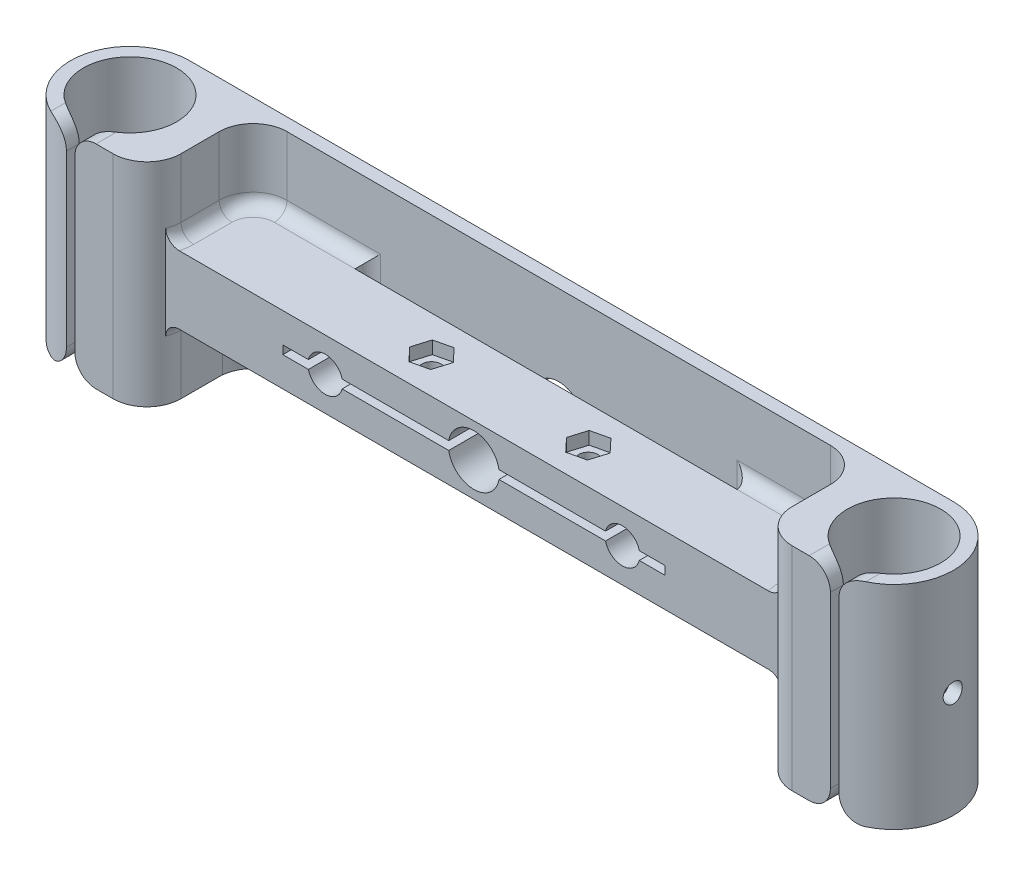
SolidWorks part; units mm, degrees
ref_plane "Front Plane" through (0, 0, 0) normal (0, 0, 1) x (1, 0, 0)
ref_plane "Top Plane" through (0, 0, 0) normal (0, 1, 0) x (1, 0, 0)
ref_plane "Right Plane" through (0, 0, 0) normal (1, 0, 0) x (0, 0, -1)
sketch "Sketch1" plane through (0, 0, 0) normal (0, 1, 0) x (1, 0, 0)
  line L0 (137.4606, -14.5) -> (119.4606, -14.5)
  line L1 (119.4606, -14.5) -> (119.4606, 10.5)
  line L2 (-42.5394, -14.5) -> (-24.5394, -14.5)
  line L3 (-42.5394, 13.5) -> (137.4606, 13.5)
  line L4 (119.4606, 10.5) -> (-24.5394, 10.5)
  line L5 (-24.5394, -14.5) -> (-24.5394, 10.5)
  circle A0 centre (-42.5394, -0.5) radius 11
  circle A1 centre (137.4606, -0.5) radius 11
  arc A2 (-42.5394, -14.5) -> (-42.5394, 13.5) centre (-42.5394, -0.5) cw
  arc A6 (137.4606, 13.5) -> (137.4606, -14.5) centre (137.4606, -0.5) cw
  dimension "D3" = 22
  dimension "D4" = 22
  dimension "D5" = 180
  dimension "D6" = 3
  dimension "D1" = 18
  dimension "D2" = 18
  dimension "D8" = 3
extrude "Boss-Extrude1" add sketch "Sketch1" along normal blind 100
fillet "Fillet1" radius 8 4 edges at (119.4606, 50, -10.5) (119.4606, 50, 14.5) (-24.5394, 50, -10.5) (-24.5394, 50, 14.5)
sketch "Sketch2" plane through (0, 0, -10.5) normal (0, 0, 1) x (1, 0, 0)
  line L0 (47.4606, 100) -> (47.4606, 0) construction
  line L1 (-16.5394, 100) -> (111.4606, 100) construction
  line L2 (-16.5394, 0) -> (111.4606, 0) construction
  circle A0 centre (12.4606, 50) radius 4.1
  circle A1 centre (82.4606, 50) radius 4.1
  circle A2 centre (47.4606, 50) radius 6
  point P10 (47.4606, 50)
  dimension "D1" = 8.2
  dimension "D2" = 8.2
  dimension "D5" = 12
  dimension "D3" = 35
  dimension "D4" = 35
extrude "Cut-Extrude1" cut sketch "Sketch2" against normal blind 10
sketch "Sketch3" plane through (0, 0, -10.5) normal (0, 0, 1) x (1, 0, 0)
  line L0 (12.4606, 58) -> (82.4606, 58)
  line L1 (12.4606, 42) -> (82.4606, 42)
  line L2 (12.4606, 58) -> (-16.5394, 58)
  line L3 (-16.5394, 100) -> (-16.5394, 0) construction
  line L4 (-16.5394, 58) -> (-28.8663, 58)
  line L5 (-28.8663, 58) -> (-28.8663, 42)
  line L6 (-28.8663, 42) -> (12.4606, 42)
  line L7 (82.4606, 58) -> (124.1494, 58)
  line L8 (124.1494, 58) -> (124.1494, 42)
  line L9 (124.1494, 42) -> (82.4606, 42)
  circle A2 centre (12.4606, 50) radius 4.1
  circle A3 centre (82.4606, 50) radius 4.1
  circle A4 centre (47.4606, 50) radius 6
  dimension "D2" = 12
extrude "Boss-Extrude2" add sketch "Sketch3" along normal blind 20
fillet "Fillet2" radius 3 14 edges at (-24.6867, 42, 8.0281) (-24.5394, 42, 2) (-22.1963, 42, -8.1569) (119.6079, 42, 8.0281) (119.4606, 42, 2) (117.1174, 42, -8.1569) (119.6079, 58, 8.0281) (119.4606, 58, 2) (-24.6867, 58, 8.0281) (-24.5394, 58, 2) (-22.1963, 58, -8.1569) (47.4606, 58, -10.5) (47.4606, 42, -10.5) (117.1174, 58, -8.1569)
sketch "Sketch4" plane through (0, 0, 9.5) normal (0, 0, 1) x (1, 0, 0)
  line L0 (47.4606, 50) -> (2.4606, 50)
  line L1 (47.4606, 50) -> (92.4606, 50)
  dimension "D1" = 45
extrude "Cut-Extrude-Thin1" cut sketch "Sketch4" against normal up to surface (20 mm away) and the other way through all thin up to face at (47.4606, 19.5, -10.5) thin type mid plane wall 2
sketch "Sketch5" plane through (0, 42, 0) normal (0, -1, 0) x (-1, 0, 0)
  line L0 (-2.4606, 7.5) -> (-47.4606, 7.5)
  line L1 (16.5394, 7.5) -> (-111.4606, 7.5) construction
  line L2 (-47.4606, 7.5) -> (-92.4606, 7.5)
  dimension "D1" = 45
  dimension "D2" = 45
extrude "Cut-Extrude-Thin2" cut sketch "Sketch5" against normal blind 20 and the other way through all thin thin type one direction wall 3
fillet "Fillet3" radius 3 2 edges at (92.4606, 50, -10.5) (2.4606, 50, -10.5)
sketch "Sketch6" plane through (0, 49, 0) normal (0, 1, 0) x (1, 0, 0)
  line L0 (16.4368, 7.5) -> (41.5445, -9.5) construction
  line L1 (41.5445, -9.5) -> (53.3767, -9.5) construction
  line L2 (53.3767, -9.5) -> (78.4844, 7.5) construction
  circle A0 centre (28.9906, -1) radius 2.25
  circle A1 centre (65.9305, -1) radius 2.25
  dimension "D1" = 4.5
  dimension "D2" = 4.5
extrude "Cut-Extrude2" cut sketch "Sketch6" against normal through all both and the other way through all
sketch "Sketch7" plane through (0, 58, 0) normal (0, 1, 0) x (1, 0, 0)
  line L1 (33.1506, -0.0263) -> (30.2274, 3.0895)
  line L2 (30.2274, 3.0895) -> (26.0674, 2.1158)
  line L3 (26.0674, 2.1158) -> (24.8307, -1.9737)
  line L4 (24.8307, -1.9737) -> (27.7539, -5.0895)
  line L5 (27.7539, -5.0895) -> (31.9138, -4.1158)
  line L6 (31.9138, -4.1158) -> (33.1506, -0.0263)
  line L7 (70.0905, -0.0263) -> (67.1673, 3.0895)
  line L8 (67.1673, 3.0895) -> (63.0073, 2.1158)
  line L9 (63.0073, 2.1158) -> (61.7706, -1.9737)
  line L10 (61.7706, -1.9737) -> (64.6938, -5.0895)
  line L11 (64.6938, -5.0895) -> (68.8537, -4.1158)
  line L12 (68.8537, -4.1158) -> (70.0905, -0.0263)
  circle A0 centre (28.9906, -1) radius 3.7 construction
  circle A1 centre (65.9305, -1) radius 3.7 construction
  dimension "D1" = 7.4
  dimension "D2" = 7.4
extrude "Cut-Extrude3" cut sketch "Sketch7" against normal blind 3
sketch "Sketch8" plane through (0, 100, 0) normal (0, 1, 0) x (1, 0, 0)
  line L6 (119.4606, 2.5) -> (119.4606, -6.5)
  line L7 (127.4606, -14.5) -> (137.4606, -14.5)
  line L8 (137.4606, 13.5) -> (-42.5394, 13.5)
  line L9 (-42.5394, -14.5) -> (-32.5394, -14.5)
  line L10 (-24.5394, -6.5) -> (-24.5394, 2.5)
  line L11 (-16.5394, 10.5) -> (111.4606, 10.5)
  line L12 (119.4606, 2.5) -> (119.4606, -6.5)
  line L13 (127.4606, -14.5) -> (137.4606, -14.5)
  line L14 (137.4606, 13.5) -> (-42.5394, 13.5)
  line L15 (-42.5394, -14.5) -> (-32.5394, -14.5)
  line L16 (-24.5394, -6.5) -> (-24.5394, 2.5)
  line L17 (-16.5394, 10.5) -> (111.4606, 10.5)
  arc A6 (119.4606, -6.5) -> (127.4606, -14.5) centre (127.4606, -6.5) ccw
  arc A7 (137.4606, -14.5) -> (137.4606, 13.5) centre (137.4606, -0.5) ccw
  arc A8 (-42.5394, 13.5) -> (-42.5394, -14.5) centre (-42.5394, -0.5) ccw
  arc A9 (-32.5394, -14.5) -> (-24.5394, -6.5) centre (-32.5394, -6.5) ccw
  arc A10 (-16.5394, 10.5) -> (-24.5394, 2.5) centre (-16.5394, 2.5) ccw
  arc A11 (119.4606, 2.5) -> (111.4606, 10.5) centre (111.4606, 2.5) ccw
  arc A12 (119.4606, -6.5) -> (127.4606, -14.5) centre (127.4606, -6.5) ccw
  arc A13 (137.4606, -14.5) -> (137.4606, 13.5) centre (137.4606, -0.5) ccw
  arc A14 (-42.5394, 13.5) -> (-42.5394, -14.5) centre (-42.5394, -0.5) ccw
  arc A15 (-32.5394, -14.5) -> (-24.5394, -6.5) centre (-32.5394, -6.5) ccw
  arc A16 (-16.5394, 10.5) -> (-24.5394, 2.5) centre (-16.5394, 2.5) ccw
  arc A17 (119.4606, 2.5) -> (111.4606, 10.5) centre (111.4606, 2.5) ccw
  dimension "D1" = 0
extrude "Cut-Extrude4" cut sketch "Sketch8" against normal blind 25
sketch "Sketch9" plane through (0, 0, 0) normal (0, 1, 0) x (1, 0, 0)
  line L6 (127.4606, -14.5) -> (137.4606, -14.5)
  line L7 (119.4606, 2.5) -> (119.4606, -6.5)
  line L8 (-16.5394, 10.5) -> (111.4606, 10.5)
  line L9 (-24.5394, -6.5) -> (-24.5394, 2.5)
  line L10 (-42.5394, -14.5) -> (-32.5394, -14.5)
  line L11 (137.4606, 13.5) -> (-42.5394, 13.5)
  line L12 (127.4606, -14.5) -> (137.4606, -14.5)
  line L13 (119.4606, 2.5) -> (119.4606, -6.5)
  line L14 (-16.5394, 10.5) -> (111.4606, 10.5)
  line L15 (-24.5394, -6.5) -> (-24.5394, 2.5)
  line L16 (-42.5394, -14.5) -> (-32.5394, -14.5)
  line L17 (137.4606, 13.5) -> (-42.5394, 13.5)
  arc A6 (119.4606, -6.5) -> (127.4606, -14.5) centre (127.4606, -6.5) ccw
  arc A7 (119.4606, 2.5) -> (111.4606, 10.5) centre (111.4606, 2.5) ccw
  arc A8 (-16.5394, 10.5) -> (-24.5394, 2.5) centre (-16.5394, 2.5) ccw
  arc A9 (-32.5394, -14.5) -> (-24.5394, -6.5) centre (-32.5394, -6.5) ccw
  arc A10 (-42.5394, 13.5) -> (-42.5394, -14.5) centre (-42.5394, -0.5) ccw
  arc A11 (137.4606, -14.5) -> (137.4606, 13.5) centre (137.4606, -0.5) ccw
  arc A12 (119.4606, -6.5) -> (127.4606, -14.5) centre (127.4606, -6.5) ccw
  arc A13 (119.4606, 2.5) -> (111.4606, 10.5) centre (111.4606, 2.5) ccw
  arc A14 (-16.5394, 10.5) -> (-24.5394, 2.5) centre (-16.5394, 2.5) ccw
  arc A15 (-32.5394, -14.5) -> (-24.5394, -6.5) centre (-32.5394, -6.5) ccw
  arc A16 (-42.5394, 13.5) -> (-42.5394, -14.5) centre (-42.5394, -0.5) ccw
  arc A17 (137.4606, -14.5) -> (137.4606, 13.5) centre (137.4606, -0.5) ccw
  dimension "D1" = 0
extrude "Cut-Extrude5" cut sketch "Sketch9" along normal blind 25
ref_plane "Plane1" through (-42.5394, 0, 0) normal (1, 0, 0) x (0, 0, -1)
sketch "Sketch10" plane through (-42.5394, 0, 0) normal (1, 0, 0) x (0, 0, -1)
  line L0 (-11.5, 25) -> (-11.5, 75)
  line L1 (10.5, 75) -> (10.5, 25)
  line L2 (10.5, 75) -> (10.5, 25)
  line L3 (-11.5, 25) -> (-11.5, 75)
  line L4 (10.5, 25) -> (-11.5, 75) construction
  circle A0 centre (-0.5, 50) radius 2.25
  dimension "D1" = 4.5
extrude "Cut-Extrude6" cut sketch "Sketch10" against normal blind 53 and the other way blind 39 contours L4 A0 | A0 L4 region at (-42.5394, 49.6154, 1.3741) region at (-42.5394, 50.3846, -0.3741)
sketch "Sketch11" plane through (-24.5394, 0, 0) normal (1, 0, 0) x (0, 0, -1)
  line L0 (3.25, 47.8349) -> (3.25, 16.9854)
  line L1 (3.25, 16.9854) -> (-4.25, 16.9854)
  line L3 (3.25, 47.8349) -> (3.25, 52.1651)
  line L4 (3.25, 52.1651) -> (-0.5, 54.3301)
  line L5 (-0.5, 54.3301) -> (-4.25, 52.1651)
  line L6 (-4.25, 52.1651) -> (-4.25, 47.8349)
  line L8 (-4.25, 16.9854) -> (-4.25, 47.8349)
  line L10 (-0.5, 45.6699) -> (1.375, 46.7524) [skipped]
  line L11 (-4.25, 47.8349) -> (-2.375, 46.7524) [skipped]
  arc A0 (3.25, 50) -> (-2.375, 46.7524) centre (-0.5, 50) ccw construction
  dimension "D1" = 7.5
extrude "Cut-Extrude7" cut sketch "Sketch11" along normal blind 4
ref_plane "Plane2" through (47.4606, 0, 0) normal (1, 0, 0) x (0, 0, -1)
mirror "Mirror1" about plane through (47.4606, 0, 0) normal (1, 0, 0) of "Cut-Extrude6", "Cut-Extrude7"
sketch "Sketch12" plane through (0, 0, 14.5) normal (0, 0, 1) x (1, 0, 0)
  line L0 (137.4606, 25) -> (137.4606, 75)
  line L1 (127.4606, 75) -> (137.4606, 75) construction
  line L2 (137.4606, 75) -> (137.4606, 25) construction
extrude "Cut-Extrude-Thin3" cut sketch "Sketch12" against normal blind 10 and the other way through all thin thin type mid plane wall 2
mirror "Mirror2" about plane through (47.4606, 0, 0) normal (1, 0, 0) of "Cut-Extrude-Thin3"
fillet "Fillet4" radius 5 4 edges at (-43.5394, 75, 12.9593) (-41.5394, 75, 12.9772) (-43.5394, 25, 12.9593) (-41.5394, 25, 12.9772)
fillet "Fillet5" radius 5 2 edges at (136.4606, 25, 12.9772) (138.4606, 25, 12.9593)
fillet "Fillet6" radius 5 2 edges at (138.4606, 75, 12.9593) (136.4606, 75, 12.9772)
